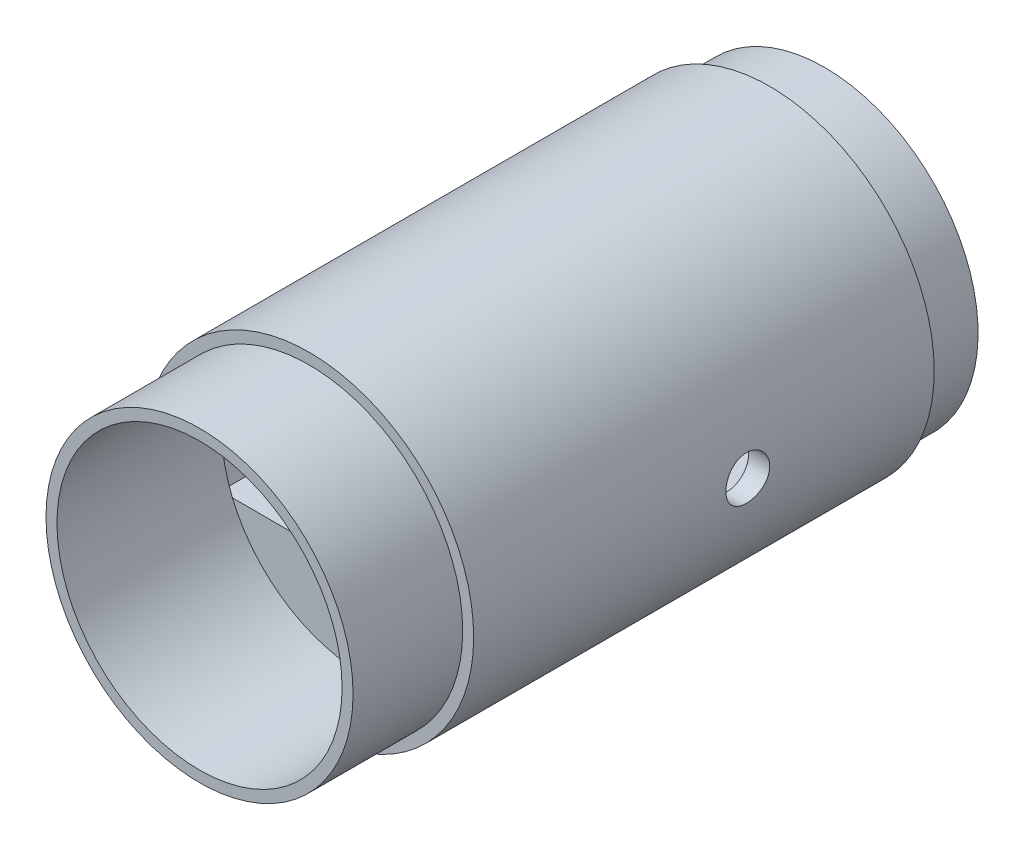
SolidWorks part; units mm, degrees
ref_plane "Alzado" through (0, 0, 0) normal (0, 0, 1) x (1, 0, 0)
ref_plane "Planta" through (0, 0, 0) normal (0, 1, 0) x (1, 0, 0)
ref_plane "Vista lateral" through (0, 0, 0) normal (1, 0, 0) x (0, 0, -1)
sketch "Croquis1" plane through (0, 0, 0) normal (0, 0, 1) x (1, 0, 0)
  line L0 (-13.0767, -5) -> (-4, -5)
  line L2 (-13.0767, 5) -> (-13.0767, -5)
  line L4 (13.0767, 5) -> (13.0767, -5)
  line L10 (-4, -13.4164) -> (-4, -14.4568)
  line L12 (4, -13.4164) -> (4, -14.4568)
  line L13 (-4, -13.4164) -> (-4, -5)
  line L14 (4, -13.4164) -> (4, -5)
  line L15 (4, -5) -> (13.0767, -5)
  arc A0 (13.0767, 5) -> (-13.0767, 5) centre (0, 0) ccw
  arc A1 (4, -14.4568) -> (-4, -14.4568) centre (0, 0) ccw
  point P8 (0, -13.4164)
  dimension "D1" = 28
  dimension "D2" = 30
  dimension "D3" = 10
  dimension "D4" = 8
extrude "Saliente-Extruir1" add sketch "Croquis1" along normal blind 10 and the other way blind 15
sketch "Croquis2" plane through (-13.0767, 0, 0) normal (1, 0, 0) x (0, 0, -1)
  circle A0 centre (0, 0) radius 2
  dimension "D1" = 4
extrude "Cortar-Extruir1" cut sketch "Croquis2" against normal blind 10 and the other way blind 40
sketch "Croquis3" plane through (0, 0, 10) normal (0, 0, 1) x (1, 0, 0)
  line L0 (-13.0767, -5) -> (13.0767, -5)
  circle A0 centre (0, 0) radius 15
  arc A1 (13.0767, -5) -> (-13.0767, -5) centre (0, 0) ccw
extrude "Saliente-Extruir2" add sketch "Croquis3" along normal blind 10
sketch "Croquis4" plane through (0, -5, 0) normal (0, 1, 0) x (1, 0, 0)
  line L0 (-13.0767, -20) -> (13.0767, -20) construction
  line L1 (-4, -20) -> (4, -20)
  line L2 (-4, -20) -> (-4, -10)
  line L3 (-4, -10) -> (4, -10)
  line L4 (4, -20) -> (4, -10)
  line L5 (-4, -20) -> (4, -10) construction
  line L6 (-4, -10) -> (4, -20) construction
  point P0 (0, -15)
  dimension "D1" = 0
extrude "Saliente-Extruir3" add sketch "Croquis4" along normal blind 5
sketch "Croquis5" plane through (0, 0, 20) normal (0, 0, 1) x (1, 0, 0)
  line L0 (-4, 0) -> (4, 0) construction
  circle A0 centre (0, 0) radius 15
  circle A1 centre (0, 0) radius 14
  dimension "D1" = 28
extrude "Saliente-Extruir5" add sketch "Croquis5" along normal blind 5
sketch "Croquis6" plane through (0, 0, 20) normal (0, 0, 1) x (1, 0, 0)
  line L0 (-4, 0) -> (4, 0) construction
  circle A0 centre (0, 0) radius 14
  circle A1 centre (0, 0) radius 13
  dimension "D1" = 28
  dimension "D2" = 26
extrude "Saliente-Extruir7" add sketch "Croquis6" along normal blind 15
sketch "Croquis8" plane through (0, 0, -15) normal (0, 0, -1) x (-1, 0, 0)
  line L0 (-4, 6.4568) -> (4, 6.4568)
  line L2 (-4, 6.4568) -> (-4, 14.4568)
  line L3 (-4, 14.4568) -> (4, 14.4568)
  line L4 (4, 6.4568) -> (4, 14.4568)
  line L5 (0, 0) -> (4, 14.4568) construction
  line L6 (-4, 14.4568) -> (0, 0) construction
  arc A0 (4, -14.4568) -> (-4, -14.4568) centre (0, 0) ccw construction
  point P0 (0, 0)
  dimension "D1" = 8
  dimension "D2" = 8
extrude "Saliente-Extruir8" add sketch "Croquis8" against normal blind 10 and the other way blind 1
sketch "Croquis9" plane through (4, 0, 0) normal (1, 0, 0) x (0, 0, -1)
  line L6 (16, 6.4568) -> (5, 6.4568)
  line L7 (5, 6.4568) -> (5, 13.4164)
  line L8 (5, 13.4164) -> (16, 6.4568)
extrude "Cortar-Extruir2" cut sketch "Croquis9" against normal up to surface (8 mm away) up to face at (-4, 11.4434, -12)
sketch "Croquis10" plane through (0, 0, -15) normal (0, 0, -1) x (-1, 0, 0)
  line L0 (4, 6.4568) -> (4, 14.4568) construction
  line L1 (-4, 12.4568) -> (4, 12.4568)
  line L2 (-4, 12.4568) -> (-4, 10.4568)
  line L3 (-4, 10.4568) -> (4, 10.4568)
  line L4 (4, 12.4568) -> (4, 10.4568)
  line L5 (-4, 12.4568) -> (4, 10.4568) construction
  line L6 (-4, 10.4568) -> (4, 12.4568) construction
  point P0 (0, 11.4568)
  dimension "D1" = 2
extrude "Cortar-Extruir3" cut sketch "Croquis10" against normal blind 2 and the other way blind 6.5
sketch "Croquis11" plane through (0, 0, -15) normal (0, 0, -1) x (-1, 0, 0)
  line L0 (-4, -13.4164) -> (-4, -14.4568)
  line L9 (4, -13.4164) -> (4, -14.4568)
  arc A0 (4, -14.4568) -> (-4, -14.4568) centre (0, 0) ccw
  arc A1 (4, -13.4164) -> (-4, -13.4164) centre (0, 0) ccw
extrude "Saliente-Extruir9" add sketch "Croquis11" along normal blind 2
sketch "Croquis12" plane through (0, 0, -17) normal (0, 0, -1) x (-1, 0, 0)
  line L0 (-4, -12.3693) -> (-4, -13.4164)
  line L9 (4, -12.3693) -> (4, -13.4164)
  arc A0 (4, -13.4164) -> (-4, -13.4164) centre (0, 0) ccw
  arc A1 (4, -12.3693) -> (-4, -12.3693) centre (0, 0) ccw
  dimension "D1" = 26
extrude "Saliente-Extruir10" add sketch "Croquis12" along normal blind 5 and the other way up to surface (2 mm away) separate body other way up to face at (7.3525, -8.158, -15)
sketch "Croquis14" plane through (0, 0, 20) normal (0, 0, 1) x (1, 0, 0)
  line L0 (0, 0) -> (0, -8.778) construction
  line L1 (-4, 0) -> (4, 0) construction
  line L2 (0, -8.778) -> (0, 0.5527) construction
  line L3 (-3.5, 0) -> (3.5, 0)
  line L4 (-3.5, 0) -> (-3.5, -7)
  line L5 (3.5, 0) -> (3.5, -7)
  line L6 (-3.5, -7) -> (-1.5, -7)
  line L7 (3.5, -7) -> (1.5, -7)
  line L8 (-1.5, -7) -> (-1.5, -3.5)
  line L9 (-1.5, -3.5) -> (1.5, -3.5)
  line L10 (1.5, -3.5) -> (1.5, -7)
  dimension "D1" = 7
  dimension "D2" = 3.5
  dimension "D3" = 7
  dimension "D4" = 7
  dimension "D5" = 2
  dimension "D6" = 2
extrude "Cortar-Extruir4" cut sketch "Croquis14" against normal blind 6.5 from offset 2 offset against normal yes
sketch "Croquis15" plane through (0, 0, 20) normal (0, 0, 1) x (1, 0, 0)
  line L0 (-4, 0) -> (4, 0) construction
  line L1 (-3.5, -2.5) -> (3.5, -2.5)
  line L2 (-3.5, -2.5) -> (-3.5, -7.5)
  line L3 (-3.5, -7.5) -> (3.5, -7.5)
  line L4 (3.5, -2.5) -> (3.5, -7.5)
  line L5 (-3.5, -2.5) -> (3.5, -7.5) construction
  line L6 (-3.5, -7.5) -> (3.5, -2.5) construction
  point P0 (0, -5)
  point P5 (0, 0)
  dimension "D1" = 5
  dimension "D2" = 7
  dimension "D3" = 5
extrude "Cortar-Extruir5" cut sketch "Croquis15" against normal up to surface (2 mm away) up to face at (0, -4.375, 18)
sketch "Croquis16" plane through (-13.0767, 0, 0) normal (1, 0, 0) x (0, 0, -1)
  line L0 (0, 0) -> (-10, 0) construction
  line L1 (-10, -5) -> (-10, 5) construction
  line L3 (2.1, -4.78) -> (-7.5, -4.78)
  line L4 (2.1, -4.78) -> (2.1, 4.78)
  line L5 (2.1, 4.78) -> (-7.5, 4.78)
  line L6 (-7.5, -4.78) -> (-7.5, 4.78)
  line L7 (2.1, -4.78) -> (-7.5, 4.78) construction
  line L8 (2.1, 4.78) -> (-7.5, -4.78) construction
  circle A0 centre (0, 0) radius 2 construction
  circle A1 centre (0, 0) radius 2
  point P5 (-2.7, 0)
  dimension "D1" = 2.1
  dimension "D2" = 9.56
  dimension "D3" = 9.6
extrude "Saliente-Extruir11" add sketch "Croquis16" against normal blind 2 contours L4 L5 L6 L3 | A1
